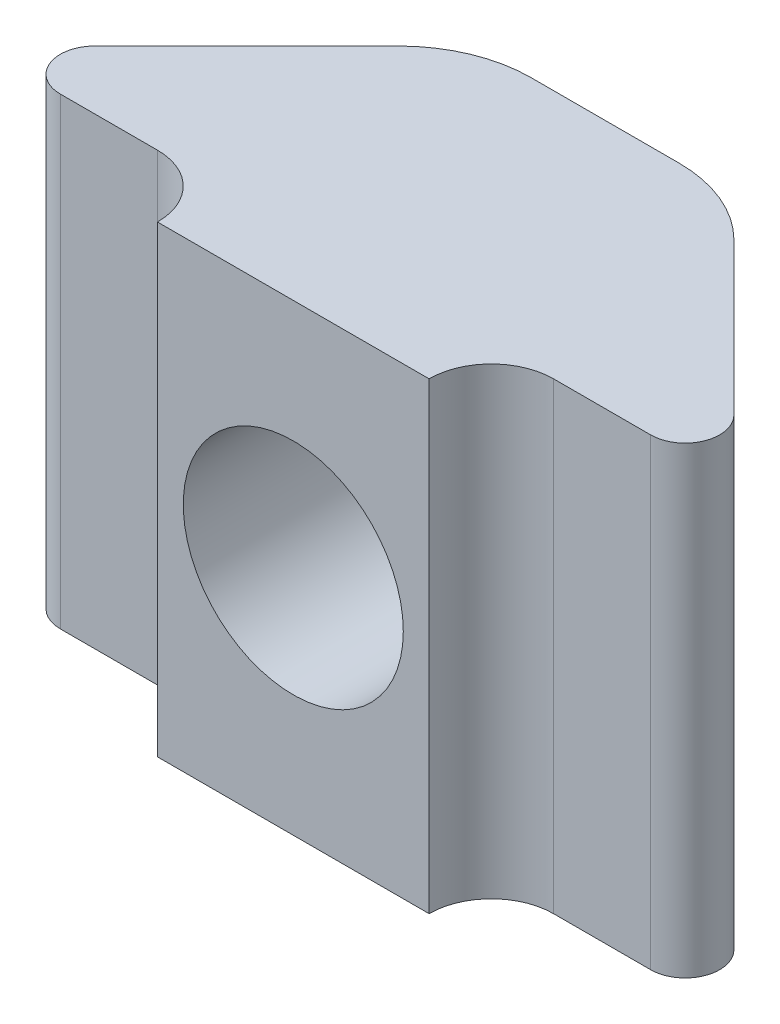
SolidWorks part; units mm, degrees
ref_plane "Front Plane" through (0, 0, 0) normal (0, 0, 1) x (1, 0, 0)
ref_plane "Top Plane" through (0, 0, 0) normal (0, 1, 0) x (1, 0, 0)
ref_plane "Right Plane" through (0, 0, 0) normal (1, 0, 0) x (0, 0, -1)
sketch "Sketch1" plane through (0, 0, 0) normal (0, 1, 0) x (1, 0, 0)
  line L10 (-2.9785, -6.8393) -> (2.9785, -6.8393)
  line L14 (6.4748, -5.4744) -> (4.3434, -5.4744)
  line L15 (3.6793, -0.8538) -> (7.0094, -4.1838)
  line L16 (-1.6181, 0) -> (1.6181, 0)
  line L17 (-7.0094, -4.1838) -> (-3.6793, -0.8538)
  line L18 (-4.3434, -5.4744) -> (-6.4748, -5.4744)
  arc A6 (4.3434, -5.4744) -> (2.9785, -6.8393) centre (4.3434, -6.8393) ccw
  arc A7 (6.4748, -5.4744) -> (7.0094, -4.1838) centre (6.4748, -4.7184) ccw
  arc A8 (3.6793, -0.8538) -> (1.6181, 0) centre (1.6181, -2.915) ccw
  arc A9 (-1.6181, 0) -> (-3.6793, -0.8538) centre (-1.6181, -2.915) ccw
  arc A10 (-7.0094, -4.1838) -> (-6.4748, -5.4744) centre (-6.4748, -4.7184) ccw
  arc A11 (-2.9785, -6.8393) -> (-4.3434, -5.4744) centre (-4.3434, -6.8393) ccw
  point P0 (0, 0)
extrude "Boss-Extrude1" add sketch "Sketch1" along normal blind 10.16
sketch "Sketch2" plane through (0, 0, 6.8393) normal (0, 0, 1) x (1, 0, 0)
  line L0 (2.9785, 10.16) -> (-2.9785, 0) construction
  line L1 (-2.9785, 10.16) -> (2.9785, 0) construction
  circle A0 centre (0, 5.08) radius 2.413
  dimension "D1" = 4.826
extrude "Cut-Extrude1" cut sketch "Sketch2" against normal through all
